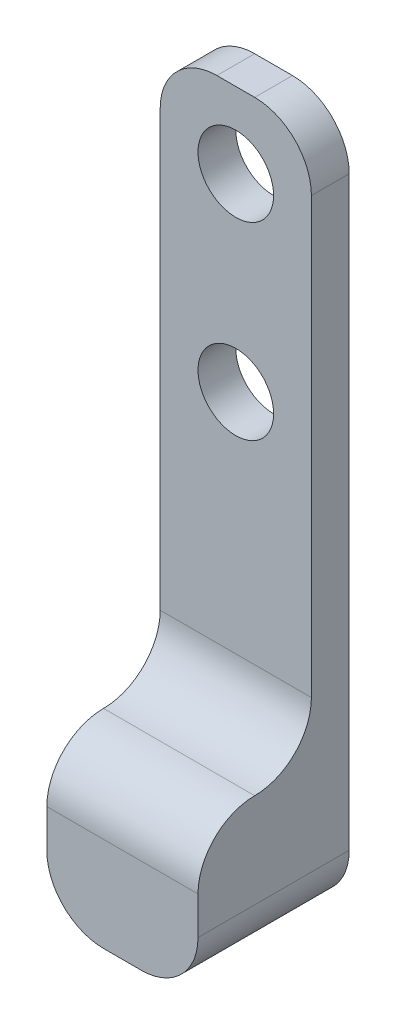
SolidWorks part; units mm, degrees
ref_plane "Front Plane" through (0, 0, 0) normal (0, 0, 1) x (1, 0, 0)
ref_plane "Top Plane" through (0, 0, 0) normal (0, 1, 0) x (1, 0, 0)
ref_plane "Right Plane" through (0, 0, 0) normal (1, 0, 0) x (0, 0, -1)
sketch "Sketch1" plane through (0, 0, 0) normal (0, 0, 1) x (1, 0, 0)
  line L1 (-27.9913, 19.2088) -> (37.0087, 19.2088)
  line L2 (-27.9913, 19.2088) -> (-27.9913, -28.7912)
  line L3 (-27.9913, -28.7912) -> (37.0087, -28.7912)
  line L4 (37.0087, 19.2088) -> (37.0087, -28.7912)
  dimension "D1" = 65
  dimension "D2" = 48
extrude "Boss-Extrude1" add sketch "Sketch1" along normal blind 2
sketch "Sketch2" plane through (0, 0, 2) normal (0, 0, 1) x (1, 0, 0)
  line L0 (37.0087, 19.2088) -> (-27.9913, 19.2088) construction
  circle A0 centre (4.5087, 4.2088) radius 1.2831
  circle A1 centre (4.5087, -5.7912) radius 1.259
  dimension "D1" = 15
  dimension "D2" = 10
hole_wizard "M3 Clearance Hole1" positions "Sketch3" profile "Sketch4" hole size "M3" standard "ANSI Metric" end condition through all
sketch "Sketch3" plane through (0, 0, 2) normal (0, 0, 1) x (1, 0, 0)
  point P0 (4.5087, 4.2088)
  point P3 (4.5087, -5.7912)
sketch "Sketch4" plane through (4.5087, 4.2088, 2) normal (1, 0, 0) x (0, -1, 0)
  line L0 (0, 0) -> (0, 2)
  line L1 (0, 2) -> (2, 2)
  line L2 (2, 2) -> (2, 0)
  line L5 (2, 0) -> (0, 0)
  line L11 (0, -6.35) -> (0, 107.95) construction
  dimension "Thru Hole Dia." = 4
  dimension "Thru Hole Depth" = 2
sketch "Sketch5" plane through (0, 0, 2) normal (0, 0, 1) x (1, 0, 0)
  line L1 (8.5087, -28.7912) -> (0.5087, -28.7912)
  line L2 (8.5087, -28.7912) -> (8.5087, -20.7912)
  line L3 (8.5087, -20.7912) -> (0.5087, -20.7912)
  line L4 (0.5087, -28.7912) -> (0.5087, -20.7912)
  line L6 (-27.9913, -28.7912) -> (37.0087, -28.7912) construction
  dimension "D1" = 8
  dimension "D2" = 8
  dimension "D3" = 4
  dimension "D4" = 0
extrude "Boss-Extrude2" add sketch "Sketch5" along normal blind 6
sketch "Sketch6" plane through (0, 0, 2) normal (0, 0, 1) x (1, 0, 0)
  line L15 (0.5087, -28.7912) -> (8.5087, -28.7912)
  line L16 (0.5087, -28.7912) -> (0.5087, 8.2088)
  line L17 (0.5087, 8.2088) -> (8.5087, 8.2088)
  line L18 (8.5087, -28.7912) -> (8.5087, 8.2088)
  dimension "D1" = 4
extrude "Cut-Extrude1" cut sketch "Sketch6" against normal through all
fillet "Fillet4" radius 3 6 edges at (8.5087, -28.7912, 4) (4.5087, -20.7912, 2) (4.5087, -20.7912, 8) (0.5087, 8.2088, 1) (8.5087, 8.2088, 1) (0.5087, -28.7912, 4)
